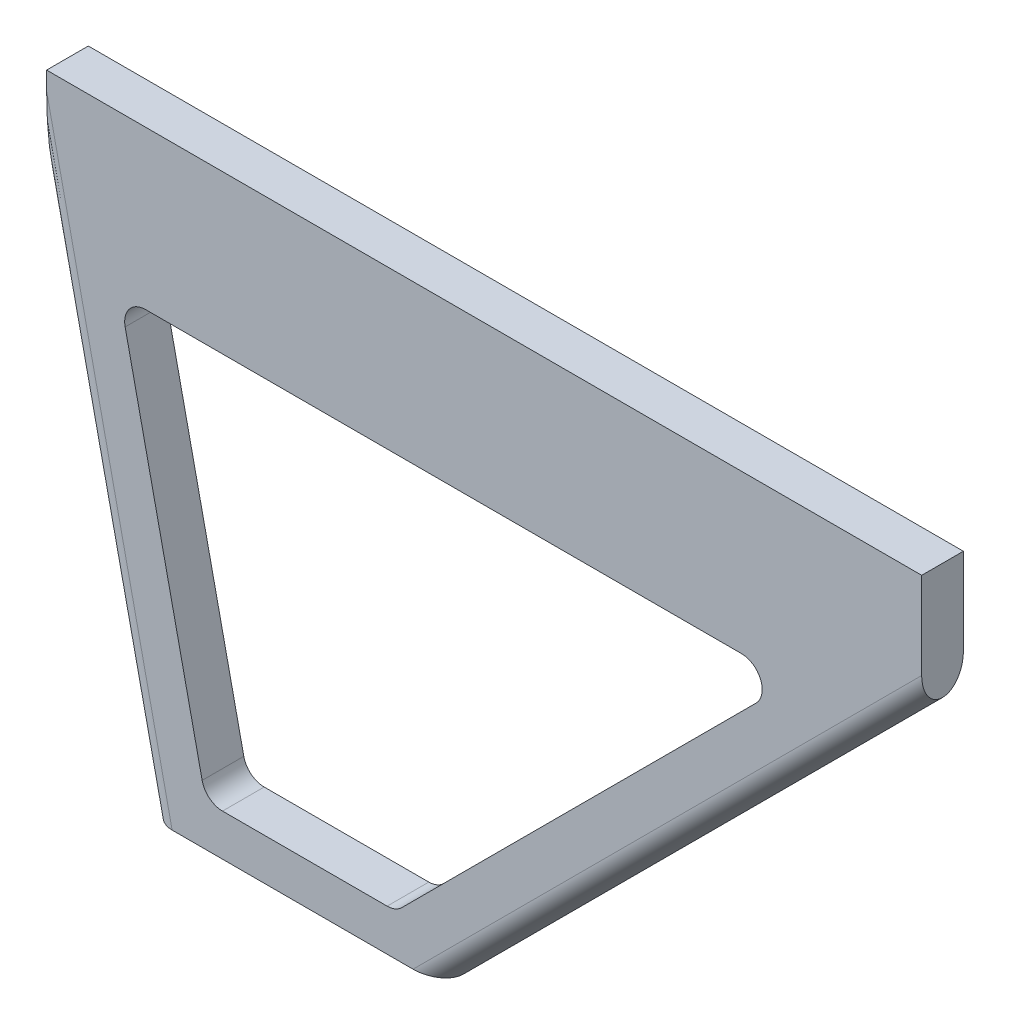
SolidWorks part; units mm, degrees
material "Zoltek Panex 33"
ref_plane "Plan de face" through (0, 0, 0) normal (0, 0, 1) x (1, 0, 0)
ref_plane "Plan de dessus" through (0, 0, 0) normal (0, 1, 0) x (1, 0, 0)
ref_plane "Plan de droite" through (0, 0, 0) normal (1, 0, 0) x (0, 0, -1)
sketch "Esquisse2" plane through (0, 0, 0) normal (0, 0, 1) x (1, 0, 0)
  line L0 (-30.1972, -50.239) -> (-5.1972, -165.239)
  line L1 (-30.1972, -50.239) -> (-30.1972, -22.339)
  line L2 (-30.1972, -22.339) -> (179.8028, -22.339)
  line L3 (179.8028, -22.339) -> (179.8028, -50.239)
  line L4 (179.8028, -50.239) -> (64.8028, -165.239)
  line L5 (64.8028, -165.239) -> (-5.1972, -165.239)
  line L6 (119.8028, -50.239) -> (869.8028, -50.239) construction
  line L7 (-30.1972, -22.339) -> (0, -22.339) construction
  line L8 (53.5896, -155.239) -> (148.5896, -60.239)
  line L9 (148.5896, -60.239) -> (-12.6729, -60.239)
  line L10 (-12.6729, -60.239) -> (7.9792, -155.239)
  line L11 (53.5896, -155.239) -> (7.9792, -155.239)
  point P11 (30.7844, -155.239)
  dimension "D1" = 210
  dimension "D2" = 70
  dimension "D3" = 45
  dimension "D4" = 115
  dimension "D5" = 15
  dimension "D6" = 10
  dimension "D7" = 15
  dimension "D8" = 10
extrude "Boss.-Extru.1" add sketch "Esquisse2" along normal mid plane 10
fillet "Fillet1" radius 5 4 edges at (148.5896, -60.239, 0) (-12.6729, -60.239, 0) (7.9792, -155.239, 0) (53.5896, -155.239, 0)
fillet "Fillet2" radius 5 4 edges at (-17.6972, -107.739, -5) (-17.6972, -107.739, 5) (122.3028, -107.739, -5) (122.3028, -107.739, 5) tangent propagation no
